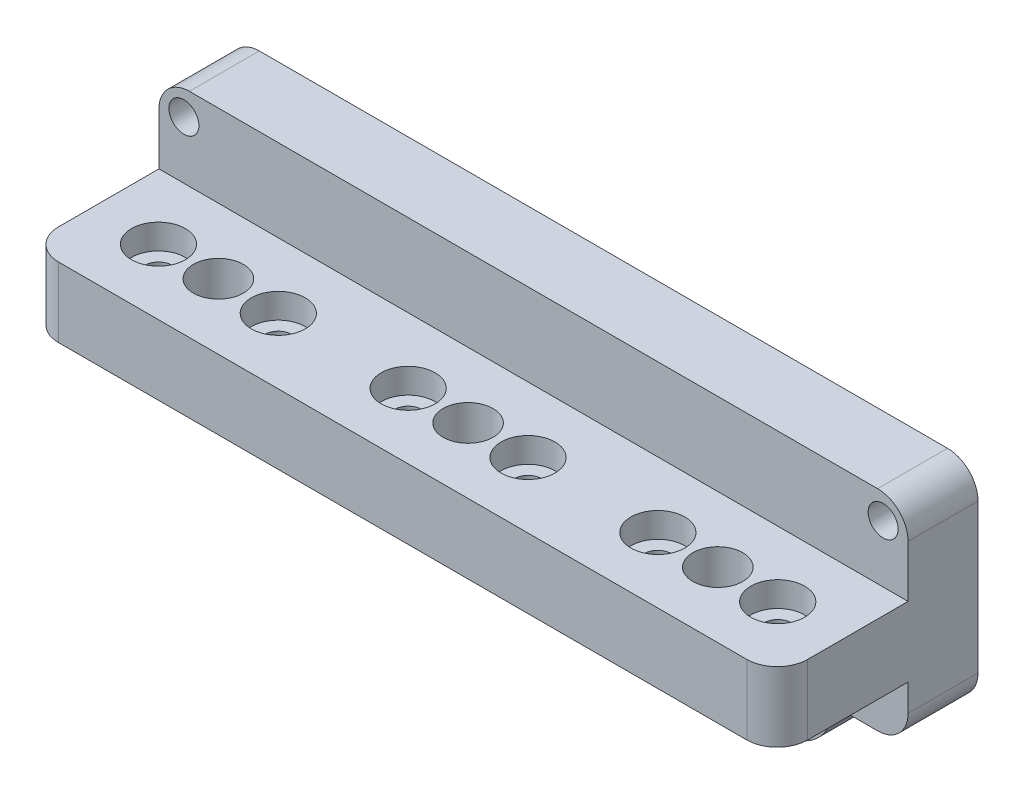
SolidWorks part; units mm, degrees
material "1060 Alloy"
ref_plane "Front Plane" through (0, 0, 0) normal (0, 0, 1) x (1, 0, 0)
ref_plane "Top Plane" through (0, 0, 0) normal (0, 1, 0) x (1, 0, 0)
ref_plane "Right Plane" through (0, 0, 0) normal (1, 0, 0) x (0, 0, -1)
sketch "Sketch1" plane through (0, 0, 0) normal (0, 0, 1) x (1, 0, 0)
  line L0 (-37.5, 0) -> (-25, 0) construction
  line L1 (37.5, -10.5) -> (30, -10.5)
  line L2 (37.5, -10.5) -> (37.5, 10.5)
  line L3 (37.5, 10.5) -> (-37.5, 10.5)
  line L4 (-37.5, -10.5) -> (-37.5, 10.5)
  line L5 (37.5, -10.5) -> (-37.5, 10.5) construction
  line L6 (37.5, 10.5) -> (-37.5, -10.5) construction
  line L7 (-30, -10.5) -> (-37.5, -10.5)
  line L8 (-25, 0) -> (-12.5, 0) construction
  line L9 (-12.5, 0) -> (0, 0) construction
  line L10 (0, 0) -> (12.5, 0) construction
  line L11 (12.5, 0) -> (25, 0) construction
  line L12 (25, 0) -> (37.5, 0) construction
  line L13 (-5, -10.5) -> (-20, -10.5)
  line L14 (20, -10.5) -> (5, -10.5)
  line L15 (-35, 10.5) -> (-35, 8) construction
  line L16 (-35, 8) -> (-37.5, 8) construction
  line L17 (-25, -10.5) -> (-25, 10.5) construction
  line L18 (-12.5, -10.5) -> (-12.5, 10.5) construction
  line L19 (12.5, -10.5) -> (12.5, 10.5) construction
  arc A0 (-20, -10.5) -> (-30, -10.5) centre (-25, -10.5) cw
  arc A1 (5, -10.5) -> (-5, -10.5) centre (0, -10.5) cw
  arc A2 (30, -10.5) -> (20, -10.5) centre (25, -10.5) cw
  circle A3 centre (-25, -10.5) radius 1.7999
  circle A4 centre (0, -10.5) radius 1.7999
  circle A5 centre (25, -10.5) radius 1.7999
  circle A6 centre (-35, 8) radius 1.5
  circle A7 centre (-15, 8) radius 1.5
  circle A8 centre (-10, 8) radius 1.5
  circle A9 centre (10, 8) radius 1.5
  circle A10 centre (35, 8) radius 1.5
  circle A11 centre (15, 8) radius 1.5
  point P0 (0, 0)
  dimension "D4" = 5
  dimension "D5" = 3.5999
  dimension "D7" = 3
  dimension "D1" = 75
  dimension "D2" = 21
  dimension "D3" = 12.5
  dimension "D6" = 2.5
extrude "Boss-Extrude1" add sketch "Sketch1" along normal blind 7
ref_plane "Plane1" through (0, 2.25, 0) normal (0, 1, 0) x (1, 0, 0)
sketch "Sketch2" plane through (0, 2.25, 0) normal (0, 1, 0) x (1, 0, 0)
  line L1 (-37.5, -13.55) -> (-12.5, -13.55) construction
  line L7 (37.5, -7) -> (-37.5, -7)
  line L8 (37.5, -7) -> (37.5, -20.1)
  line L11 (37.5, -20.1) -> (-37.5, -20.1)
  line L12 (-37.5, -7) -> (-37.5, -20.1)
  line L13 (37.5, -7) -> (-37.5, -20.1) construction
  line L14 (37.5, -20.1) -> (-37.5, -7) construction
  line L15 (-12.5, -13.55) -> (12.5, -13.55) construction
  line L16 (12.5, -13.55) -> (37.5, -13.55) construction
  line L17 (12.5, -13.55) -> (12.5, -7) construction
  line L18 (-12.5, -13.55) -> (-12.5, -7) construction
  circle A0 centre (0, -13.55) radius 2.5
  circle A1 centre (6.0001, -13.55) radius 2.6999
  circle A2 centre (-6.0001, -13.55) radius 2.6999
  circle A3 centre (6.0001, -13.55) radius 1.3498
  circle A4 centre (-6.0001, -13.55) radius 1.3498
  circle A5 centre (-18.9999, -13.55) radius 1.3498
  circle A6 centre (-18.9999, -13.55) radius 2.6999
  circle A7 centre (-25, -13.55) radius 2.5
  circle A8 centre (-31.0001, -13.55) radius 1.3498
  circle A9 centre (-31.0001, -13.55) radius 2.6999
  circle A10 centre (31.0001, -13.55) radius 1.3498
  circle A11 centre (31.0001, -13.55) radius 2.6999
  circle A12 centre (25, -13.55) radius 2.5
  circle A13 centre (18.9999, -13.55) radius 1.3498
  circle A14 centre (18.9999, -13.55) radius 2.6999
  point P4 (0, -13.55)
  dimension "D2" = 5
  dimension "D3" = 5.3999
  dimension "D6" = 2.6997
  dimension "D1" = 13.1
  dimension "D4" = 6.0001
  dimension "D5" = 6.0001
  dimension "D7" = 25
extrude "Boss-Extrude2" add sketch "Sketch2" against normal blind 6.988 contours L7 L12 L11 L8 A11 A9 A7 A2 A1 A0 A6 A12 A14 | A9 A8 | A6 A5 | A2 A4 | A1 A3 | A14 A13 | A11 A10 region at (36.7386, 2.25, 13.55) region at (3.3766, 2.25, 13.55) region at (-8.6237, 2.25, 13.55) region at (-21.6234, 2.25, 13.55) region at (-33.6237, 2.25, 13.55) region at (28.3766, 2.25, 13.55) region at (16.3763, 2.25, 13.55)
extrude "Cut-Extrude1" cut sketch "Sketch2<3>" against normal blind 2.5 contours A9 A8 | A6 A5 | A2 A4 | A1 A3 | A14 A13 | A11 A10 region at (3.3766, 2.25, 13.55) region at (-8.6237, 2.25, 13.55) region at (-21.6234, 2.25, 13.55) region at (-33.6237, 2.25, 13.55) region at (28.3766, 2.25, 13.55) region at (16.3763, 2.25, 13.55)
sketch "Sketch2<3>" plane through (0, 2.25, 0) normal (0, 1, 0) x (1, 0, 0) same geometry as "Sketch2"
ref_plane "Plane2" through (-37.5, -4.738, 7) normal (-1, 0, 0) x (0, 0, 1)
sketch "Sketch7" plane through (0, 0, 0) normal (0, 0, -1) x (-1, 0, 0)
  line L0 (-37.5, 10.5) -> (37.5, 10.5) construction
  line L1 (-23.4221, 10.5) -> (22.3327, 10.5)
  line L2 (-23.4221, 10.5) -> (-23.4221, 3.1212)
  line L3 (-23.4221, 3.1212) -> (22.3327, 3.1212)
  line L4 (22.3327, 10.5) -> (22.3327, 3.1212)
  line L5 (-23.4221, 10.5) -> (22.3327, 3.1212) construction
  line L6 (-23.4221, 3.1212) -> (22.3327, 10.5) construction
  line L8 (-3.0348, -7.6949) -> (2.7235, -7.6949)
  line L9 (-3.0348, -7.6949) -> (-3.0348, -12.6751)
  line L10 (-3.0348, -12.6751) -> (2.7235, -12.6751)
  line L11 (2.7235, -7.6949) -> (2.7235, -12.6751)
  line L12 (-3.0348, -7.6949) -> (2.7235, -12.6751) construction
  line L13 (-3.0348, -12.6751) -> (2.7235, -7.6949) construction
  point P4 (-0.5447, 6.8106)
  point P11 (-0.1556, -10.185)
extrude "Boss-Extrude4" add sketch "Sketch7" against normal up to surface (7 mm away) up to face at (-33.5, 8, 7)
sketch "Sketch8" plane through (0, 0, 7) normal (0, 0, 1) x (1, 0, 0)
  line L0 (-20, -10.5) -> (-5, -10.5) construction
  line L1 (-5, -10.5) -> (10.9381, -10.5)
  line L2 (-5, -10.5) -> (-5, -21.1132)
  line L3 (-5, -21.1132) -> (10.9381, -21.1132)
  line L4 (10.9381, -10.5) -> (10.9381, -21.1132)
  line L5 (-5, -10.5) -> (10.9381, -21.1132) construction
  line L6 (-5, -21.1132) -> (10.9381, -10.5) construction
  arc A0 (-5, -10.5) -> (5, -10.5) centre (0, -10.5) ccw construction
  point P4 (2.9691, -15.8066)
extrude "Cut-Extrude3" cut sketch "Sketch8" against normal blind 21.288
fillet "Fillet3" radius 3.048 6 edges at (37.5, -1.244, 20.1) (-37.5, -1.244, 20.1) (37.5, 10.5, 3.5) (37.5, -10.5, 3.5) (-37.5, -10.5, 3.5) (-37.5, 10.5, 3.5)
sketch "Sketch4" plane through (0, 0, 7) normal (0, 0, 1) x (1, 0, 0)
  line L0 (37.5, -4.738) -> (-37.5, -4.738) construction
  line L1 (-12.5, -4.738) -> (12.5, -4.738)
  line L2 (-12.5, -4.738) -> (-12.5, -19.8028)
  line L3 (-12.5, -19.8028) -> (12.5, -19.8028)
  line L4 (12.5, -4.738) -> (12.5, -19.8028)
  line L5 (-12.5, -4.738) -> (12.5, -19.8028) construction
  line L6 (-12.5, -19.8028) -> (12.5, -4.738) construction
  point P4 (0, -12.2704)
  dimension "D1" = 25
extrude "Cut-Extrude2" cut sketch "Sketch4" against normal blind 38.822
